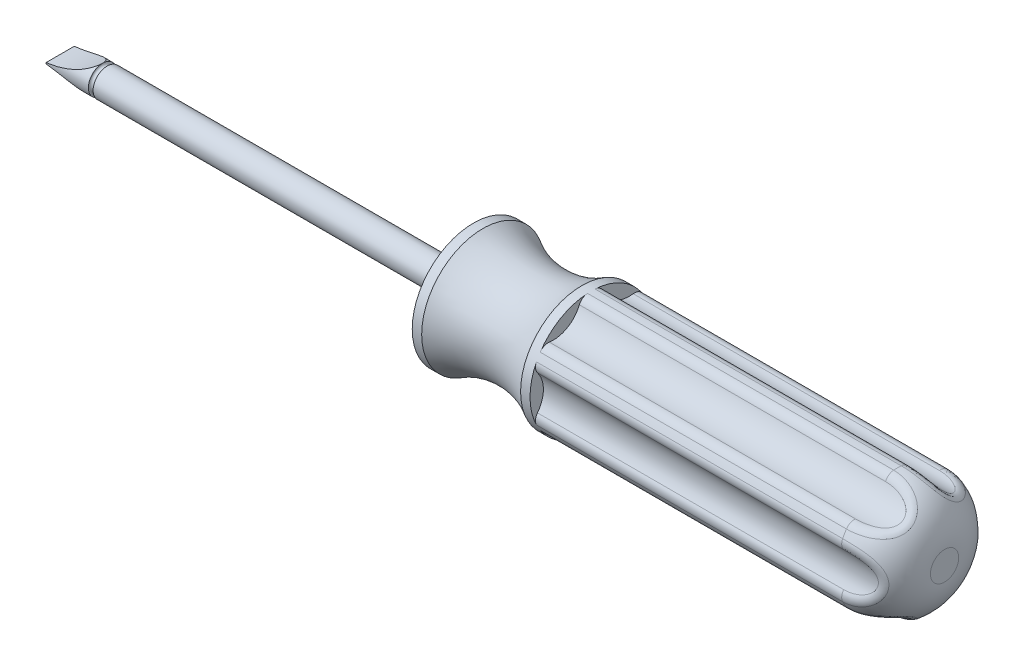
SolidWorks part; units mm, degrees
ref_plane "Front Plane" through (0, 0, 0) normal (0, 0, 1) x (1, 0, 0)
ref_plane "Top Plane" through (0, 0, 0) normal (0, 1, 0) x (1, 0, 0)
ref_plane "Right Plane" through (0, 0, 0) normal (1, 0, 0) x (0, 0, -1)
sketch "Sketch1" plane through (0, 0, 0) normal (0, 0, 1) x (1, 0, 0)
  line L0 (0, 3) -> (0, 13)
  line L1 (0, 13) -> (2.0038, 13)
  line L2 (25.0077, 13) -> (90.0077, 13)
  line L3 (23.0038, 13) -> (25.0077, 13)
  line L4 (100.0077, 3) -> (100.0077, 0)
  line L5 (0, 3) -> (-87.74, 3)
  line L6 (-87.74, 3) -> (-87.74, 0)
  line L7 (-87.74, 0) -> (100.0077, 0)
  arc A0 (2.0038, 13) -> (23.0038, 13) centre (12.5038, 30.022) ccw
  arc A1 (90.0077, 13) -> (100.0077, 3) centre (90.0077, 3) cw
  dimension "D4" = 20
  dimension "D7" = 10
  dimension "D1" = 3
  dimension "D2" = 10
  dimension "D3" = 12.5038
  dimension "D5" = 21
  dimension "D6" = 3
  dimension "D8" = 75
  dimension "D9" = 87.74
revolve "Revolve1" add sketch "Sketch1" angle 360 about L7
sketch "Sketch2" plane through (100.0077, 0, 0) normal (1, 0, 0) x (0, 0, -1)
  arc A0 (-12.1963, 4.5) -> (-12.1963, -4.5) centre (-16.1649, 0) cw
  circle A1 centre (0, 0) radius 13 construction
  arc A2 (-2.201, 12.8123) -> (-9.9953, 8.3123) centre (-8.0825, 13.9992) cw
  arc A3 (9.9953, 8.3123) -> (2.201, 12.8123) centre (8.0825, 13.9992) cw
  arc A4 (12.1963, -4.5) -> (12.1963, 4.5) centre (16.1649, 0) cw
  arc A5 (2.201, -12.8123) -> (9.9953, -8.3123) centre (8.0825, -13.9992) cw
  arc A6 (-9.9953, -8.3123) -> (-2.201, -12.8123) centre (-8.0825, -13.9992) cw
  arc A7 (-12.1963, 4.5) -> (-12.1963, -4.5) centre (0, 0) ccw
  arc A8 (-2.201, 12.8123) -> (-9.9953, 8.3123) centre (0, 0) ccw
  arc A9 (9.9953, 8.3123) -> (2.201, 12.8123) centre (0, 0) ccw
  arc A10 (12.1963, -4.5) -> (12.1963, 4.5) centre (0, 0) ccw
  arc A11 (2.201, -12.8123) -> (9.9953, -8.3123) centre (0, 0) ccw
  arc A12 (-9.9953, -8.3123) -> (-2.201, -12.8123) centre (0, 0) ccw
  point P3 (-10.1649, 0)
  point P25 (0, 0)
  dimension "D1" = 6
  dimension "D2" = 9
  dimension "D3" = 6
extrude "Cut-Extrude1" cut sketch "Sketch2" against normal blind 75
fillet "Fillet1" radius 2 18 edges at (57.5077, -12.8123, -2.201) (57.5077, -8.3123, -9.9953) (57.5077, -8.3123, 9.9953) (57.5077, -12.8123, 2.201) (57.5077, 4.5, 12.1963) (57.5077, -4.5, 12.1963) (57.5077, 12.8123, 2.201) (57.5077, 8.3123, 9.9953) (57.5077, 8.3123, -9.9953) (57.5077, 12.8123, -2.201) (57.5077, -4.5, -12.1963) (57.5077, 4.5, -12.1963) (96.9826, -8.8467, -5.0081) (96.9826, -8.7605, 5.1575) (96.9826, 0.0862, 10.1656) (96.9826, 8.8467, 5.0081) (96.9826, 8.7605, -5.1575) (96.9826, -0.0862, -10.1656)
sketch "Sketch3" plane through (0, 0, 0) normal (0, 0, 1) x (1, 0, 0)
  line L0 (0, 3) -> (-87.74, 3) construction
  line L1 (-87.74, 3) -> (-87.74, -3) construction
  line L2 (-78.74, 3) -> (-87.74, 3)
  line L3 (-87.74, 3) -> (-87.74, 0.125)
  line L4 (14.3, 0) -> (-14.3, 0) construction
  line L5 (-78.74, -3) -> (-87.74, -3)
  line L6 (-87.74, -3) -> (-87.74, -0.125)
  line L7 (0, 0) -> (-87.74, 0)
  arc A0 (-78.74, 3) -> (-87.74, 0.125) centre (-90.7103, 24.9479) cw
  arc A1 (-78.74, -3) -> (-87.74, -0.125) centre (-90.7103, -24.9479) ccw
  circle A2 centre (-78.24, 3) radius 0.5
  dimension "D3" = 25
  dimension "D4" = 1
  dimension "D1" = 9
  dimension "D2" = 2.875
extrude "Cut-Extrude2" cut sketch "Sketch3" against normal mid plane 12 contours A0 L2 L3 | L5 A1 L6 region at (-84.46, 1.9244, 0) region at (-84.46, -1.9244, 0)
revolve "Cut-Revolve1" cut sketch "Sketch3<4>" angle 360 about L7
sketch "Sketch3<4>" plane through (0, 0, 0) normal (0, 0, 1) x (1, 0, 0) same geometry as "Sketch3"
